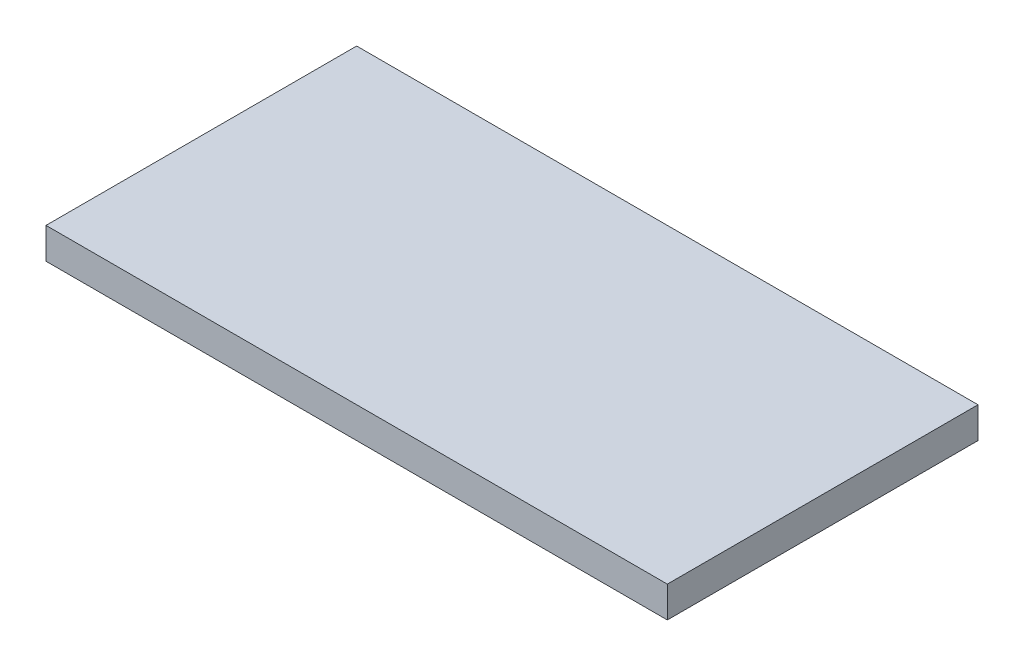
SolidWorks part; units mm, degrees
ref_plane "Front Plane" through (0, 0, 0) normal (0, 0, 1) x (1, 0, 0)
ref_plane "Top Plane" through (0, 0, 0) normal (0, 1, 0) x (1, 0, 0)
ref_plane "Right Plane" through (0, 0, 0) normal (1, 0, 0) x (0, 0, -1)
sketch "Sketch1" plane through (0, 0, 0) normal (0, 1, 0) x (1, 0, 0)
  line L1 (-25.4, -12.7) -> (25.4, -12.7)
  line L2 (-25.4, -12.7) -> (-25.4, 12.7)
  line L3 (-25.4, 12.7) -> (25.4, 12.7)
  line L4 (25.4, -12.7) -> (25.4, 12.7)
  line L5 (-25.4, -12.7) -> (25.4, 12.7) construction
  line L6 (-25.4, 12.7) -> (25.4, -12.7) construction
  point P0 (0, 0)
  dimension "D1" = 25.4
  dimension "D2" = 50.8
extrude "Boss-Extrude1" add sketch "Sketch1" along normal blind 2.54
